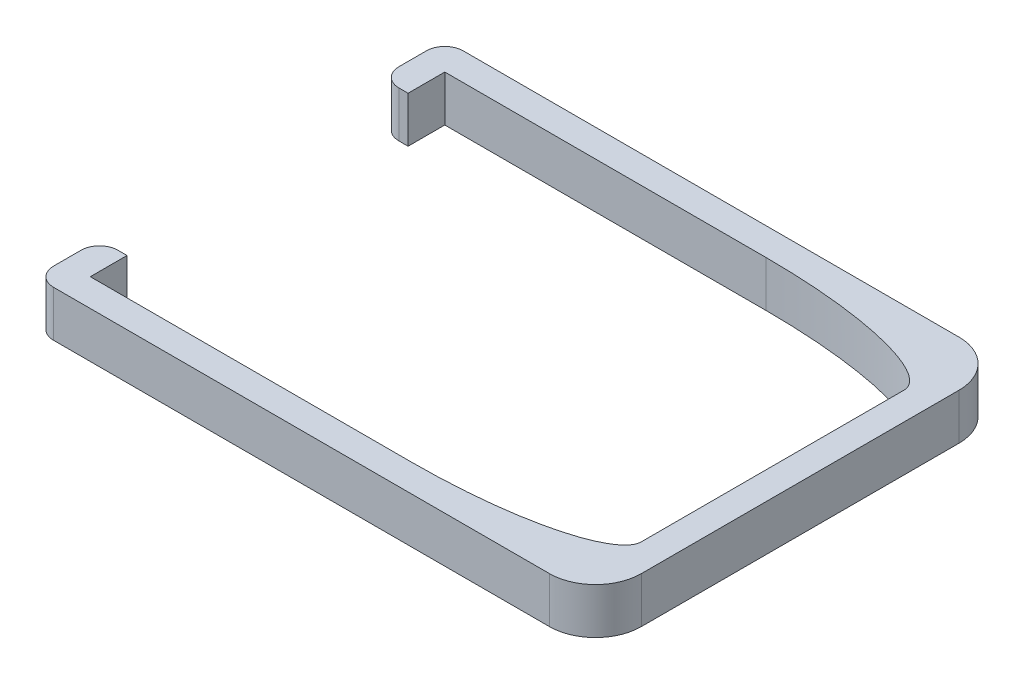
SolidWorks part; units mm, degrees
ref_plane "Front Plane" through (0, 0, 0) normal (0, 0, 1) x (1, 0, 0)
ref_plane "Top Plane" through (0, 0, 0) normal (0, 1, 0) x (1, 0, 0)
ref_plane "Right Plane" through (0, 0, 0) normal (1, 0, 0) x (0, 0, -1)
sketch "Sketch1" plane through (0, 0, 0) normal (0, 1, 0) x (1, 0, 0)
  line L0 (0, 0) -> (55, 0)
  line L1 (55, 0) -> (55, -38.6)
  line L2 (55, -38.6) -> (0, -38.6)
  line L4 (1.5, -41.6) -> (58, -41.6)
  line L5 (58, -41.6) -> (58, 3)
  line L6 (58, 3) -> (0, 3)
  line L8 (0, 3) -> (-3, 3)
  line L9 (-3, 3) -> (-3, -4)
  line L10 (-3, -4) -> (0, -4)
  line L11 (0, -4) -> (0, 0)
  line L12 (0, -38.6) -> (0, -34.6)
  line L13 (0, -34.6) -> (-3, -34.6)
  line L14 (-3, -34.6) -> (-3, -41.6)
  line L15 (-3, -41.6) -> (1.5, -41.6)
  dimension "D1" = 55
  dimension "D2" = 38.6
  dimension "D3" = 3
  dimension "D4" = 3
  dimension "D5" = 3
  dimension "D6" = 3
  dimension "D7" = 4
  dimension "D8" = 3
  dimension "D9" = 4
extrude "Boss-Extrude1" add sketch "Sketch1" along normal blind 5
fillet "Fillet1" radius 5 2 edges at (55, 2.5, 0) (55, 2.5, 38.6) second distance 20 first distance on face at (55, 2.5, 19.3)
fillet "Fillet2" radius 2 4 edges at (-3, 2.5, 34.6) (-3, 2.5, 4) (-3, 2.5, -3) (-3, 2.5, 41.6)
fillet "Fillet3" radius 5 2 edges at (58, 2.5, 41.6) (58, 2.5, -3)
